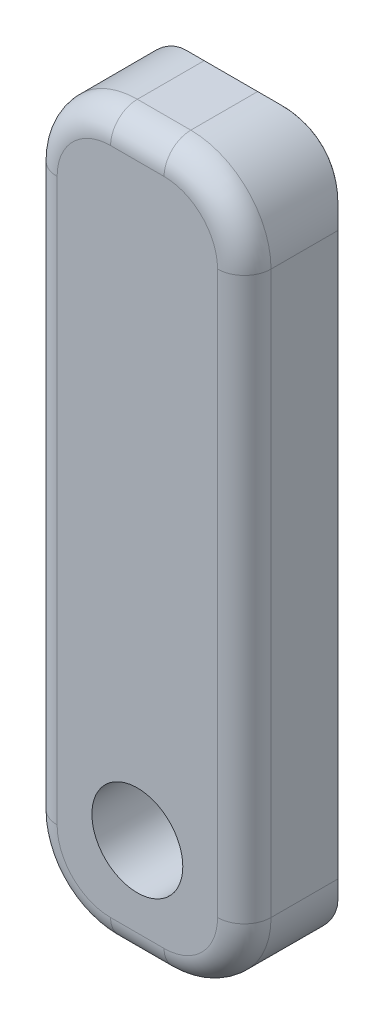
SolidWorks part; units mm, degrees
material "ABS"
ref_plane "Front Plane" through (0, 0, 0) normal (0, 0, 1) x (1, 0, 0)
ref_plane "Top Plane" through (0, 0, 0) normal (0, 1, 0) x (1, 0, 0)
ref_plane "Right Plane" through (0, 0, 0) normal (1, 0, 0) x (0, 0, -1)
sketch "Sketch1" plane through (0, 0, 0) normal (0, 0, 1) x (1, 0, 0)
  line L1 (-4, 13.5) -> (4, 13.5)
  line L2 (-4, 13.5) -> (-4, -13.5)
  line L3 (-4, -13.5) -> (4, -13.5)
  line L4 (4, 13.5) -> (4, -13.5)
  line L5 (-4, 13.5) -> (4, -13.5) construction
  line L6 (-4, -13.5) -> (4, 13.5) construction
  circle A0 centre (0, -9.5) radius 1.7
  point P0 (0, 0)
  dimension "D1" = 3.4
  dimension "D2" = 8
  dimension "D3" = 4
  dimension "D4" = 13.5
extrude "Boss-Extrude1" add sketch "Sketch1" along normal blind 5
chamfer "Chamfer1" distance 1.5 angle 45 4 edges at (0, -13.5, 0) (-4, 0, 0) (0, 13.5, 0) (4, 0, 0)
fillet "Fillet1" radius 1 4 edges at (0, -13.5, 5) (4, 0, 5) (-4, 0, 5) (0, 13.5, 5)
fillet "Fillet2" radius 3 12 edges at (-3.7071, 13.2071, 4.7071) (-3.7071, -13.2071, 4.7071) (3.7071, -13.2071, 4.7071) (3.7071, 13.2071, 4.7071) (3.25, -12.75, 0.75) (-3.25, -12.75, 0.75) (-3.25, 12.75, 0.75) (3.25, 12.75, 0.75) (4, 13.5, 2.75) (4, -13.5, 2.75) (-4, -13.5, 2.75) (-4, 13.5, 2.75)
